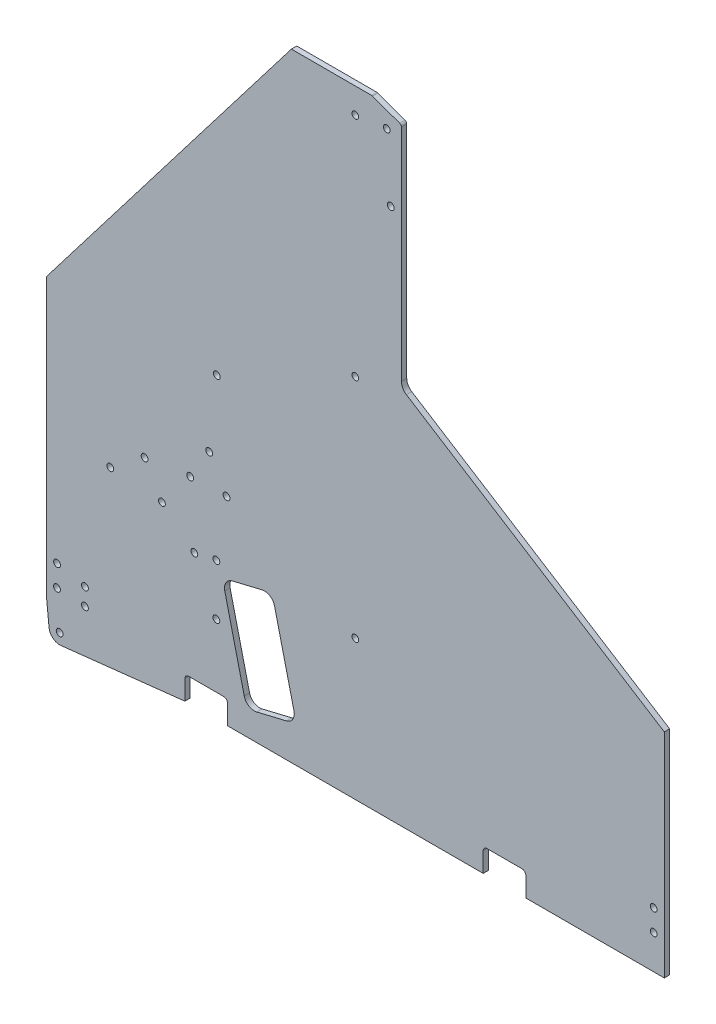
SolidWorks part; units mm, degrees
ref_plane "Front Plane" through (0, 0, 0) normal (0, 0, 1) x (1, 0, 0)
ref_plane "Top Plane" through (0, 0, 0) normal (0, 1, 0) x (1, 0, 0)
ref_plane "Right Plane" through (0, 0, 0) normal (1, 0, 0) x (0, 0, -1)
sketch "Sketch1" plane through (0, 0, 0) normal (0, 0, 1) x (1, 0, 0)
  line L0 (82.55, -20.32) -> (82.55, -6.35)
  line L2 (0, 0) -> (0, 157.48)
  line L4 (368.3, -20.32) -> (368.3, 106.68)
  line L5 (82.55, -6.35) -> (107.95, -6.35)
  line L6 (107.95, -6.35) -> (107.95, -20.32)
  line L7 (107.95, -20.32) -> (260.35, -20.32)
  line L8 (260.35, -20.32) -> (260.35, -6.35)
  line L9 (260.35, -6.35) -> (285.75, -6.35)
  line L10 (285.75, -6.35) -> (285.75, -20.32)
  line L11 (285.75, -20.32) -> (368.3, -20.32)
  line L12 (361.95, 12.7) -> (368.3, 12.7) construction
  line L13 (0, 0) -> (6.35, 0) construction
  line L14 (0.0315, -6.9818) -> (1.619, -22.8568)
  line L15 (8.6391, -28.5361) -> (82.55, -20.32)
  line L16 (0, 0) -> (0, -6.35)
  line L17 (85.725, 97.155) -> (82.9754, 95.5675) construction
  line L18 (97.0634, 115.6163) -> (58.5686, 93.3913) construction
  line L19 (97.0634, 115.6163) -> (107.3822, 97.7437) construction
  line L20 (58.5686, 93.3913) -> (68.8873, 75.5187) construction
  line L21 (107.3822, 97.7437) -> (68.8873, 75.5187) construction
  line L22 (97.0634, 115.6163) -> (68.8873, 75.5187) construction
  line L23 (58.5686, 93.3913) -> (107.3822, 97.7437) construction
  line L24 (7.9375, -22.225) -> (88.2169, 59.1366) construction
  line L25 (184.15, 62.98) -> (184.15, 197.98) construction
  line L26 (184.15, 197.98) -> (184.15, 332.98) construction
  line L27 (355.6, 335.28) -> (330.2, 335.28) construction
  line L28 (330.2, 335.28) -> (330.2, 220.98) construction
  line L29 (330.2, 220.98) -> (355.6, 220.98) construction
  line L30 (355.6, 220.98) -> (355.6, 335.28) construction
  line L31 (184.15, 347.98) -> (184.15, 269.4703) construction
  line L32 (12.7, 335.28) -> (38.1, 335.28) construction
  line L33 (38.1, 335.28) -> (38.1, 220.98) construction
  line L34 (12.7, 220.98) -> (12.7, 335.28) construction
  line L35 (38.1, 220.98) -> (12.7, 220.98) construction
  line L36 (194.15, 347.98) -> (211.6138, 341.63)
  line L37 (184.15, 347.98) -> (146.05, 347.98)
  line L38 (184.15, 347.98) -> (194.15, 347.98)
  line L39 (348.5362, 347.98) -> (413.4623, 347.98)
  line L40 (348.5362, 347.98) -> (211.6138, 347.98) construction
  line L42 (146.05, 347.98) -> (0, 157.48)
  line L44 (211.6138, 341.63) -> (211.6138, 205.74)
  line L45 (211.6138, 205.74) -> (368.3, 106.68)
  line L46 (194.15, 347.98) -> (-141.0713, 347.98) construction
  circle A0 centre (6.35, 0) radius 2.032
  circle A1 centre (6.35, 12.7) radius 2.032
  circle A2 centre (361.95, 0) radius 2.032
  circle A3 centre (361.95, 12.7) radius 2.032
  arc A5 (1.619, -22.8568) -> (8.6391, -28.5361) centre (7.9375, -22.225) ccw
  circle A6 centre (7.9375, -22.225) radius 2.032
  arc A7 (0, -6.35) -> (0.0315, -6.9818) centre (6.35, -6.35) ccw
  circle A8 centre (38.1, 78.105) radius 2.032
  circle A9 centre (85.725, 97.155) radius 2.032
  circle A10 centre (58.5686, 93.3913) radius 2.032
  circle A11 centre (68.8873, 75.5187) radius 2.032
  circle A12 centre (107.3822, 97.7437) radius 2.032
  circle A13 centre (97.0634, 115.6163) radius 2.032
  circle A14 centre (88.2169, 59.1366) radius 2.032
  circle A15 centre (184.15, 62.98) radius 2
  circle A16 centre (184.15, 197.98) radius 2
  circle A17 centre (184.15, 332.98) radius 2
  circle A18 centre (63.5, 316.23) radius 2.032
  circle A19 centre (101.6, 157.48) radius 2.032
  circle A20 centre (355.6, 335.28) radius 2.032
  circle A21 centre (330.2, 335.28) radius 2.032
  circle A22 centre (355.6, 220.98) radius 2.032
  circle A23 centre (330.2, 220.98) radius 2.032
  circle A24 centre (12.7, 335.28) radius 2.032
  circle A25 centre (38.1, 335.28) radius 2.032
  circle A26 centre (12.7, 220.98) radius 2.032
  circle A27 centre (38.1, 220.98) radius 2.032
  circle A28 centre (202.8819, 335.28) radius 2
  circle A29 centre (205.2638, 296.418) radius 2.032
  point P82 (184.15, 347.98)
  point P83 (202.8819, 344.805)
  dimension "D6" = 4.064
  dimension "D10" = 6.35
  dimension "D11" = 4.064
  dimension "D17" = 38.1
  dimension "D27" = 4
  dimension "D31" = 4.064
  dimension "D32" = 38.1
  dimension "D36" = 4.064
  dimension "D47" = 45.212
  dimension "D48" = 4.064
  dimension "D2" = 127
  dimension "D3" = 13.97
  dimension "D4" = 25.4
  dimension "D5" = 152.4
  dimension "D7" = 12.7
  dimension "D8" = 6.35
  dimension "D9" = 20.32
  dimension "D12" = 22.225
  dimension "D13" = 1.5875
  dimension "D14" = 82.55
  dimension "D15" = 368.3
  dimension "D16" = 6.35
  dimension "D18" = 98.425
  dimension "D19" = 47.625
  dimension "D20" = 19.05
  dimension "D21" = 3.175
  dimension "D22" = 60
  dimension "D23" = 20.6375
  dimension "D24" = 44.45
  dimension "D25" = 38.1
  dimension "D26" = 114.3
  dimension "D28" = 135
  dimension "D29" = 12.7
  dimension "D30" = 15
  dimension "D33" = 63.5
  dimension "D34" = 27.4638
  dimension "D35" = 101.6
  dimension "D37" = 114.3
  dimension "D38" = 25.4
  dimension "D39" = 12.7
  dimension "D40" = 157.48
  dimension "D41" = 142.24
  dimension "D42" = 368.3
  dimension "D43" = 10
  dimension "D44" = 6.35
  dimension "D45" = 31.75
  dimension "D46" = 6.35
  dimension "D49" = 6.35
extrude "Boss-Extrude1" add sketch "Sketch1" along normal blind 3.175 contours L16 A7 L14 A5 L15 L2 A0 A1 A6 region at (167.243, 117.6611, 0)
fillet "Fillet1" radius 2.286 4 edges at (285.75, -6.35, 1.5875) (107.95, -6.35, 1.5875) (260.35, -6.35, 1.5875) (82.55, -6.35, 1.5875)
fillet "Fillet2" radius 6.35 1 edges at (211.6138, 205.74, 1.5875)
sketch "Sketch2" plane through (0, 0, 0) normal (0, 0, -1) x (-1, 0, 0)
  circle A0 centre (-101.3398, 61.8475) radius 2.032 construction
  circle A1 centre (-101.3398, 31.3675) radius 2.032 construction
  circle A2 centre (-23.012, 8.964) radius 2.032 construction
  circle A3 centre (-23.012, -1.196) radius 2.032 construction
  circle A4 centre (-101.3398, 61.8475) radius 2.032
  circle A5 centre (-101.3398, 31.3675) radius 2.032
  circle A6 centre (-23.012, 8.964) radius 2.032
  circle A7 centre (-23.012, -1.196) radius 2.032
extrude "Cut-Extrude1" cut sketch "Sketch2" against normal through all
fillet "Fillet3" radius 1.5875 2 edges at (211.6138, 341.63, 1.5875) (194.15, 347.98, 1.5875)
sketch "Sketch3" plane through (0, 0, 3.175) normal (0, 0, 1) x (1, 0, 0)
  line L0 (133.7394, 54.026) -> (133.5085, 54.9896) construction
  line L1 (129.1684, 57.6512) -> (111.4698, 53.4086) construction
  line L2 (115.3002, 49.1851) -> (127.6692, 52.1501) construction
  line L3 (108.8082, 49.0686) -> (109.0392, 48.1051) construction
  line L4 (131.9876, 48.4644) -> (140.8034, 11.688) construction
  line L5 (144.8863, 7.5251) -> (133.7394, 54.026) construction
  line L6 (109.0392, 48.1051) -> (120.1861, 1.6041) construction
  line L7 (121.9379, 7.1657) -> (113.1221, 43.9421) construction
  line L8 (120.1861, 1.6041) -> (120.4171, 0.6406) construction
  line L9 (145.1173, 6.5615) -> (144.8863, 7.5251) construction
  line L10 (138.6253, 6.445) -> (126.2564, 3.48) construction
  line L11 (124.7571, -2.0211) -> (142.4557, 2.2215) construction
  line L12 (133.7394, 54.026) -> (133.5085, 54.9896)
  line L13 (129.1684, 57.6512) -> (111.4698, 53.4086)
  line L14 (115.3002, 49.1851) -> (127.6692, 52.1501)
  line L15 (108.8082, 49.0686) -> (109.0392, 48.1051)
  line L16 (131.9876, 48.4644) -> (140.8034, 11.688)
  line L17 (144.8863, 7.5251) -> (133.7394, 54.026)
  line L18 (109.0392, 48.1051) -> (120.1861, 1.6041)
  line L19 (121.9379, 7.1657) -> (113.1221, 43.9421)
  line L20 (120.1861, 1.6041) -> (120.4171, 0.6406)
  line L21 (145.1173, 6.5615) -> (144.8863, 7.5251)
  line L22 (138.6253, 6.445) -> (126.2564, 3.48)
  line L23 (124.7571, -2.0211) -> (142.4557, 2.2215)
  line L24 (128.5763, 60.1212) -> (110.8777, 55.8786)
  line L25 (106.3382, 48.4765) -> (106.5692, 47.513)
  line L26 (106.5692, 47.513) -> (117.7161, 1.012)
  line L27 (117.7161, 1.012) -> (117.947, 0.0485)
  line L28 (125.3492, -4.4911) -> (143.0478, -0.2485)
  line L29 (147.5873, 7.1536) -> (147.3564, 8.1172)
  line L30 (147.3564, 8.1172) -> (136.2095, 54.6181)
  line L31 (136.2095, 54.6181) -> (135.9785, 55.5817)
  arc A0 (133.5085, 54.9896) -> (129.4178, 57.7017) centre (130.0076, 54.1504) ccw construction
  arc A1 (111.4698, 53.4086) -> (111.2247, 53.3406) centre (112.309, 49.9078) ccw construction
  arc A2 (129.4178, 57.7017) -> (129.1684, 57.6512) centre (130.0076, 54.1504) ccw construction
  arc A3 (111.2247, 53.3406) -> (108.8082, 49.0686) centre (112.309, 49.9078) ccw construction
  arc A4 (120.4171, 0.6406) -> (124.5077, -2.0716) centre (123.9179, 1.4797) ccw construction
  arc A5 (142.7009, 2.2895) -> (145.1173, 6.5615) centre (141.6165, 5.7223) ccw construction
  arc A6 (142.4557, 2.2215) -> (142.7009, 2.2895) centre (141.6165, 5.7223) ccw construction
  arc A7 (124.5077, -2.0716) -> (124.7571, -2.0211) centre (123.9179, 1.4797) ccw construction
  arc A8 (133.5085, 54.9896) -> (129.4178, 57.7017) centre (130.0076, 54.1504) ccw
  arc A9 (111.4698, 53.4086) -> (111.2247, 53.3406) centre (112.309, 49.9078) ccw
  arc A10 (129.4178, 57.7017) -> (129.1684, 57.6512) centre (130.0076, 54.1504) ccw
  arc A11 (111.2247, 53.3406) -> (108.8082, 49.0686) centre (112.309, 49.9078) ccw
  arc A12 (120.4171, 0.6406) -> (124.5077, -2.0716) centre (123.9179, 1.4797) ccw
  arc A13 (142.7009, 2.2895) -> (145.1173, 6.5615) centre (141.6165, 5.7223) ccw
  arc A14 (142.4557, 2.2215) -> (142.7009, 2.2895) centre (141.6165, 5.7223) ccw
  arc A15 (124.5077, -2.0716) -> (124.7571, -2.0211) centre (123.9179, 1.4797) ccw
  arc A16 (110.8777, 55.8786) -> (110.4596, 55.7626) centre (112.309, 49.9078) ccw
  arc A17 (110.4596, 55.7626) -> (106.3382, 48.4765) centre (112.309, 49.9078) ccw
  arc A18 (117.947, 0.0485) -> (124.9239, -4.5773) centre (123.9179, 1.4797) ccw
  arc A19 (124.9239, -4.5773) -> (125.3492, -4.4911) centre (123.9179, 1.4797) ccw
  arc A20 (143.0478, -0.2485) -> (143.4659, -0.1325) centre (141.6165, 5.7223) ccw
  arc A21 (143.4659, -0.1325) -> (147.5873, 7.1536) centre (141.6165, 5.7223) ccw
  arc A22 (135.9785, 55.5817) -> (129.0017, 60.2074) centre (130.0076, 54.1504) ccw
  arc A23 (129.0017, 60.2074) -> (128.5763, 60.1212) centre (130.0076, 54.1504) ccw
  ellipse E0 centre (125.3844, 39.6102) end of major axis (129.3246, 52.1192) minor radius 6 (131.9876, 48.4644) -> (127.6692, 52.1501) ccw construction
  ellipse E1 centre (123.0219, 39.0439) end of major axis (113.8388, 48.407) minor radius 6 (115.3002, 49.1851) -> (113.1221, 43.9421) ccw construction
  ellipse E2 centre (128.5411, 16.0199) end of major axis (132.4812, 28.5289) minor radius 6 (121.9379, 7.1657) -> (126.2564, 3.48) ccw construction
  ellipse E3 centre (130.9036, 16.5863) end of major axis (140.0868, 7.2231) minor radius 6 (138.6253, 6.445) -> (140.8034, 11.688) ccw construction
  ellipse E4 centre (125.3844, 39.6102) end of major axis (121.4443, 27.1012) minor radius 6 (131.9876, 48.4644) -> (127.6692, 52.1501) ccw
  ellipse E5 centre (123.0219, 39.0439) end of major axis (113.8388, 48.407) minor radius 6 (115.3002, 49.1851) -> (113.1221, 43.9421) ccw
  ellipse E6 centre (128.5411, 16.0199) end of major axis (132.4812, 28.5289) minor radius 6 (121.9379, 7.1657) -> (126.2564, 3.48) ccw
  ellipse E7 centre (130.9036, 16.5863) end of major axis (140.0868, 7.2231) minor radius 6 (138.6253, 6.445) -> (140.8034, 11.688) ccw
  dimension "D1" = 2.54
extrude "Cut-Extrude2" cut sketch "Sketch3" against normal through all contours A22 A23 L24 A16 A17 L25 L26 L27 A18 A19 L28 A20 A21 L29 L30 L31 A15 A12 L20 L18 L15 A11 A9 L13 A10 A8 L12 L17 L21 A13 A14 L23 | A12 A15 L23 A14 A13 L21 L17 L12 A8 A10 L13 A9 A11 L15 L18 L20 E7 L22 E6 L19 E5 L14 E4 L16 | L22 E7 L16 E4 L14 E5 L19 E6 region at (138.631, 30.6121, 3.175) region at (126.9628, 27.8151, 3.175) region at (128.9414, 59.4122, 3.175)
